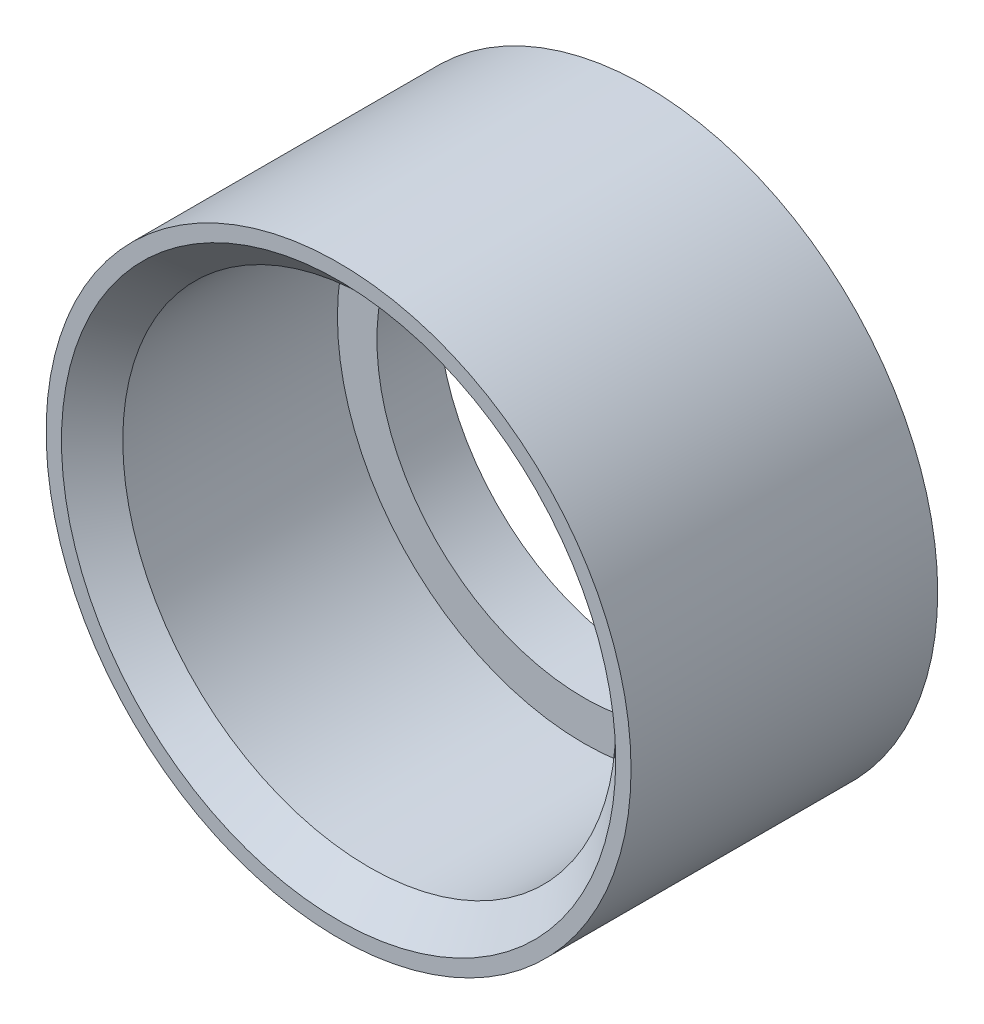
SolidWorks part; units mm, degrees
material "ABS"
ref_plane "Front Plane" through (0, 0, 0) normal (0, 0, 1) x (1, 0, 0)
ref_plane "Top Plane" through (0, 0, 0) normal (0, 1, 0) x (1, 0, 0)
ref_plane "Right Plane" through (0, 0, 0) normal (1, 0, 0) x (0, 0, -1)
sketch "Sketch1" plane through (0, 0, 0) normal (0, 0, 1) x (1, 0, 0)
  circle A0 centre (0, 0) radius 9.5375
  circle A1 centre (0, 0) radius 8.0375
  circle A2 centre (0, 0) radius 6.75
  dimension "D1" = 16.075
  dimension "D2" = 1.5
  dimension "D3" = 13.5
extrude "Boss-Extrude1" add sketch "Sketch1" along normal mid plane 10 contours A0 A1 region at (-9.2677, 0, 0)
extrude "Boss-Extrude2" add sketch "Sketch1<3>" along normal blind 2 from surface contours A1 A2 region at (-7.8102, 0, 0) starting at face at (8.0375, 0, -5)
sketch "Sketch1<3>" plane through (0, 0, 0) normal (0, 0, 1) x (1, 0, 0) same geometry as "Sketch1"
chamfer "Chamfer1" distance 1 angle 45 1 edges at (8.0375, 0, 5)
